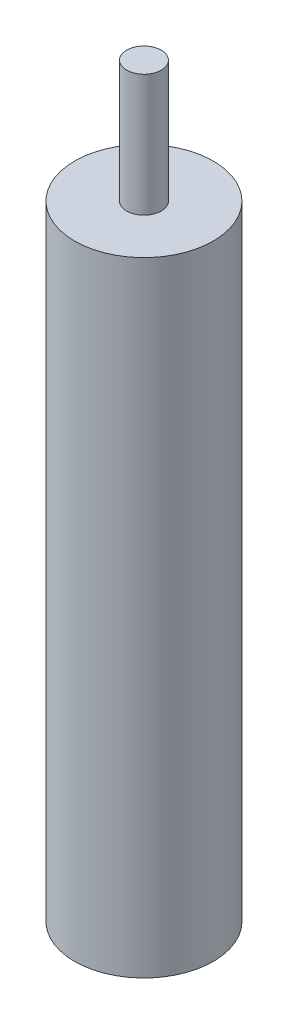
SolidWorks part; units mm, degrees
ref_plane "Front Plane" through (0, 0, 0) normal (0, 0, 1) x (1, 0, 0)
ref_plane "Top Plane" through (0, 0, 0) normal (0, 1, 0) x (1, 0, 0)
ref_plane "Right Plane" through (0, 0, 0) normal (1, 0, 0) x (0, 0, -1)
sketch "Sketch1" plane through (0, 0, 0) normal (0, 1, 0) x (1, 0, 0)
  circle A0 centre (0, 0) radius 12.7
  dimension "D1" = 25.4
extrude "Boss-Extrude1" add sketch "Sketch1" along normal blind 114.3
sketch "Sketch2" plane through (0, 114.3, 0) normal (0, 1, 0) x (1, 0, 0)
  circle A0 centre (0, 0) radius 3.175
  dimension "D1" = 6.35
extrude "Boss-Extrude2" add sketch "Sketch2" along normal blind 22.352
